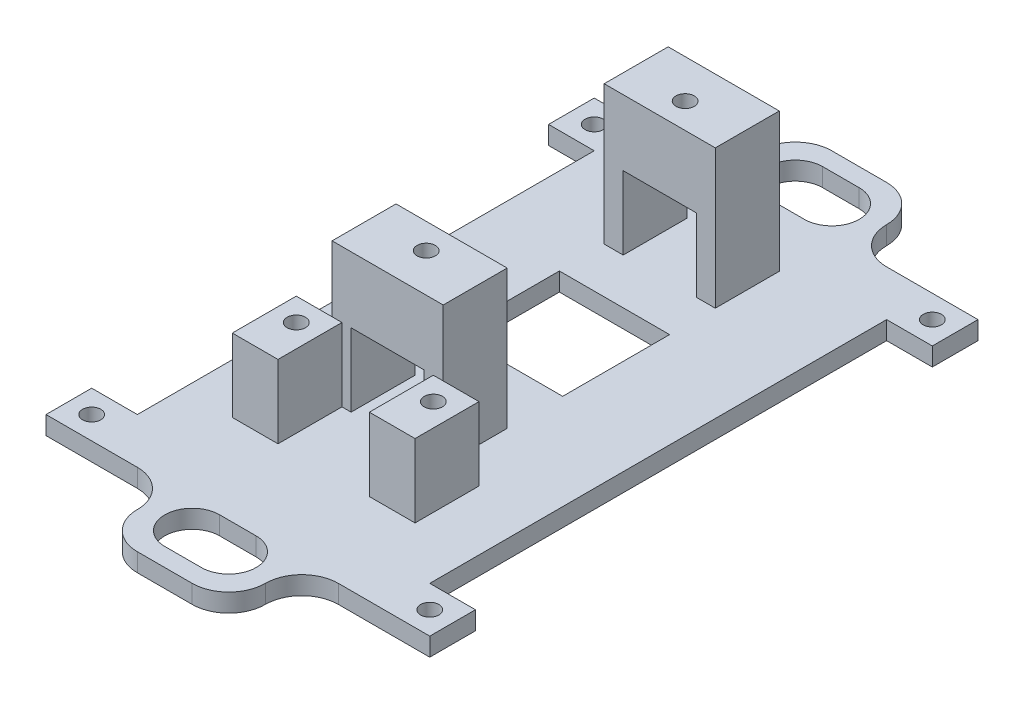
SolidWorks part; units mm, degrees
material "ABS"
ref_plane "Alzado" through (0, 0, 0) normal (0, 0, 1) x (1, 0, 0)
ref_plane "Planta" through (0, 0, 0) normal (0, 1, 0) x (1, 0, 0)
ref_plane "Vista lateral" through (0, 0, 0) normal (1, 0, 0) x (0, 0, -1)
sketch "Croquis1" plane through (0, 0, 0) normal (0, 1, 0) x (1, 0, 0)
  line L0 (0, 0) -> (0, 49.7436) construction
  line L1 (0, 0) -> (70.1538, 0) construction
  line L9 (-14, 28) -> (-16, 28)
  line L10 (-16, 28) -> (-16, -30)
  line L11 (-16, -30) -> (16, -30)
  line L12 (16, -30) -> (16, 30)
  line L13 (16, 30) -> (-16, 30)
  line L14 (-16, 30) -> (-16, 28)
  line L15 (16, 30) -> (21, 30)
  line L16 (21, 30) -> (21, 25)
  line L17 (21, 25) -> (16, 25)
  line L18 (16, 25) -> (16, 30)
  line L19 (-16, 30) -> (-21, 30)
  line L20 (-21, 30) -> (-21, 25)
  line L21 (-21, 25) -> (-16, 25)
  line L22 (-16, 25) -> (-16, 30)
  line L23 (-16, -30) -> (-21, -30)
  line L24 (-21, -30) -> (-21, -25)
  line L25 (-21, -25) -> (-16, -25)
  line L26 (-16, -25) -> (-16, -30)
  line L27 (16, -30) -> (21, -30)
  line L28 (21, -30) -> (21, -25)
  line L29 (21, -25) -> (16, -25)
  circle A0 centre (-18.5, 27.5) radius 1
  circle A1 centre (18.5, 27.5) radius 1
  circle A2 centre (18.5, -27.5) radius 1
  circle A3 centre (-18.5, -27.5) radius 1
  dimension "D1" = 2
  dimension "D2" = 2.5
  dimension "D3" = 2.5
extrude "Saliente-Extruir2" add sketch "Croquis1" along normal blind 2 contours L13 L14 L10 L11 L12 | L20 L21 L10 L14 L19 A0 | L17 L16 L15 L12 A1 | L28 L29 L12 L27 A2 | L25 L24 L23 L10 A3 region at (0, 0, 0) region at (-16.0707, 0, -26.5) region at (-16.0707, 0, 27.5) region at (18.5, 0, -29.9293) region at (16.0707, 0, 27.5)
sketch "Croquis2" plane through (0, 2, 0) normal (0, 1, 0) x (1, 0, 0)
  line L0 (0, 0) -> (22.9836, 0) construction
  line L1 (-0.5306, 0) -> (-0.5306, 30.977) construction
  line L2 (-6.6106, 0) -> (-6.6106, 16.7)
  line L3 (-0.5306, 16.7) -> (5.5494, 16.7)
  line L4 (5.5494, 16.7) -> (5.5494, 0)
  line L5 (5.5494, 0) -> (5.5494, -6.08)
  line L6 (5.5494, -6.08) -> (-0.5306, -6.08)
  line L7 (-0.5306, -6.08) -> (-6.6106, -6.08)
  line L8 (-6.6106, -6.08) -> (-6.6106, 0)
  line L9 (-6.6106, 16.7) -> (-0.5306, 16.7)
  line L10 (-6.6106, 16.7) -> (-6.6106, 23.7)
  line L11 (-6.6106, 23.7) -> (5.5494, 23.7)
  line L12 (5.5494, 23.7) -> (5.5494, 16.7)
  line L13 (-6.6106, -6.08) -> (-6.6106, -13.08)
  line L14 (-6.6106, -13.08) -> (5.5494, -13.08)
  line L15 (5.5494, -13.08) -> (5.5494, -6.08)
  dimension "D1" = 16.7
  dimension "D2" = 6.08
  dimension "D3" = 6.08
  dimension "D4" = 6.08
  dimension "D7" = 7
extrude "Saliente-Extruir3" add sketch "Croquis2" along normal blind 15.2 contours L12 L11 L10 L9 L3 | L14 L15 L6 L7 L13 region at (-0.5306, 2, -20.2) region at (-0.5306, 2, 9.58)
sketch "Croquis3" plane through (0, 17.2, 0) normal (0, 1, 0) x (1, 0, 0)
  line L0 (-6.6106, 16.7) -> (5.5494, 16.7) construction
  line L1 (-6.6106, 16.7) -> (-6.6106, 23.7) construction
  line L2 (5.5494, -6.08) -> (-6.6106, -6.08) construction
  circle A1 centre (-0.5306, 19.48) radius 1
  circle A2 centre (-0.5306, -8.86) radius 1
  dimension "D1" = 2.78
  dimension "D3" = 2.78
  dimension "D2" = 6.08
extrude "Cortar-Extruir1" cut sketch "Croquis3" against normal blind 8
sketch "Croquis4" plane through (0, 2, 0) normal (0, 1, 0) x (1, 0, 0)
  line L0 (9.4694, -13.08) -> (-10.5306, -13.08)
  line L2 (-6.6106, -13.08) -> (5.5494, -13.08) construction
  line L3 (-10.5306, -13.08) -> (-10.5306, -20.08)
  line L4 (-10.5306, -20.08) -> (-5.5306, -20.08)
  line L5 (-5.5306, -20.08) -> (-5.5306, -13.08)
  line L6 (-0.5306, -13.08) -> (-0.5306, 0.1996) construction
  line L7 (9.4694, -20.08) -> (4.4694, -20.08)
  line L8 (4.4694, -20.08) -> (4.4694, -13.08)
  line L9 (9.4694, -13.08) -> (9.4694, -20.08)
  circle A0 centre (-8.0306, -15.58) radius 1
  circle A1 centre (6.9694, -15.58) radius 1
  point P15 (-0.5306, -13.08)
  line M27 (5.5494, -13.08) -> (-6.6106, -13.08)
  dimension "D2" = 2.5
  dimension "D4" = 2
  dimension "D1" = 5
  dimension "D3" = 2.5
extrude "Saliente-Extruir4" add sketch "Croquis4" along normal blind 8 contours L4 L5 L0 L3 A0 | L9 L0 L8 L7 A1 M27 region at (6.9694, 2, 16.6786) region at (-8.0306, 2, 16.6786)
sketch "Croquis5" plane through (0, 0, 13.08) normal (0, 0, 1) x (1, 0, 0)
  line L0 (-0.5306, 2) -> (-4.5306, 2)
  line L1 (-5.5306, 2) -> (4.4694, 2) construction
  line L2 (-4.5306, 2) -> (-4.5306, 10)
  line L3 (-4.5306, 10) -> (3.4694, 10)
  line L4 (3.4694, 10) -> (3.4694, 2)
  line L5 (3.4694, 2) -> (-4.5306, 2)
  line M1 (-5.5306, 2) -> (4.4694, 2)
extrude "Cortar-Extruir2" cut sketch "Croquis5" against normal through all both and the other way through all contours L4 L3 L2 M1 region at (-0.5306, 6, 13.08)
sketch "Croquis6" plane through (0, 2, 0) normal (0, 1, 0) x (1, 0, 0)
  line L0 (0, 0) -> (32.413, 0) construction
  line L1 (0, -1000) -> (0, 0) construction
  line L2 (21, 30) -> (-21, 30) construction
  line L6 (5, 30) -> (3.5, 30)
  line L8 (-2, 36) -> (0, 36)
  line L9 (0, 36) -> (2, 36)
  line L15 (-3.5, 30) -> (-5, 30)
  line L16 (7, -30) -> (-7, -30)
  line L17 (0, 38) -> (0, 1044.4974) construction
  line L18 (-3.5, 30) -> (-2, 30)
  line L19 (3.5, 30) -> (2, 30)
  line L20 (-7, 30) -> (-7, 34)
  line L21 (-3, 38) -> (3, 38)
  line L22 (7, 34) -> (7, 30)
  line L23 (7, 30) -> (-7, 30)
  line L24 (7, -34) -> (7, -30)
  line L25 (-3, -38) -> (3, -38)
  line L26 (-7, -30) -> (-7, -34)
  line L27 (3.5, -30) -> (2, -30)
  line L28 (-3.5, -30) -> (-2, -30)
  line L29 (-3.5, -30) -> (-5, -30)
  line L30 (0, -36) -> (2, -36)
  line L31 (-2, -36) -> (0, -36)
  line L32 (5, -30) -> (3.5, -30)
  arc A3 (5, 33) -> (2, 36) centre (2, 33) ccw
  arc A5 (-2, 36) -> (-5, 33) centre (-2, 33) ccw
  arc A6 (-3, 38) -> (-7, 34) centre (-3, 34) ccw
  arc A7 (-2, 36) -> (-2, 30) centre (-2, 33) ccw
  arc A9 (2, 30) -> (2, 36) centre (2, 33) ccw
  arc A10 (7, 34) -> (3, 38) centre (3, 34) ccw
  arc A11 (7, -34) -> (3, -38) centre (3, -34) cw
  arc A12 (2, -30) -> (2, -36) centre (2, -33) cw
  arc A13 (-2, -36) -> (-2, -30) centre (-2, -33) cw
  arc A14 (-3, -38) -> (-7, -34) centre (-3, -34) cw
  arc A15 (-2, -36) -> (-5, -33) centre (-2, -33) cw
  arc A16 (5, -33) -> (2, -36) centre (2, -33) cw
  line M28 (-21, -30) -> (21, -30)
  line M34 (21, 30) -> (-21, 30)
  dimension "D7" = 4
  dimension "D3" = 4
  dimension "D4" = 3
extrude "Saliente-Extruir6" add sketch "Croquis6" against normal blind 2 contours L22 A10 L21 A6 L20 A7 A5 L8 L9 A3 A9 M34 | A14 L25 A11 L24 L16 A12 L30 L31 A13 L26 M28 region at (4.25, 2, -30.1612) region at (6.8388, 2, 32)
fillet "Redondeo1" radius 4 4 edges at (-7, 1, 30) (7, 1, 30) (7, 1, -30) (-7, 1, -30)
sketch "Croquis7" plane through (0, 2, 0) normal (0, 1, 0) x (1, 0, 0)
  line L0 (0, 0) -> (-6.5143, 0)
  line L1 (-6.5143, 0) -> (-6.5143, 11.7)
  line L2 (-6.5143, 11.7) -> (0, 11.7)
  line L3 (0, 11.7) -> (5.5457, 11.7)
  line L4 (5.5457, 11.7) -> (5.5457, 0)
  line L5 (5.5457, 0) -> (0, 0)
  line L7 (-6.6106, 16.7) -> (5.5494, 16.7) construction
  dimension "D1" = 5
  dimension "D2" = 12.06
extrude "Cortar-Extruir3" cut sketch "Croquis7" against normal blind 10
